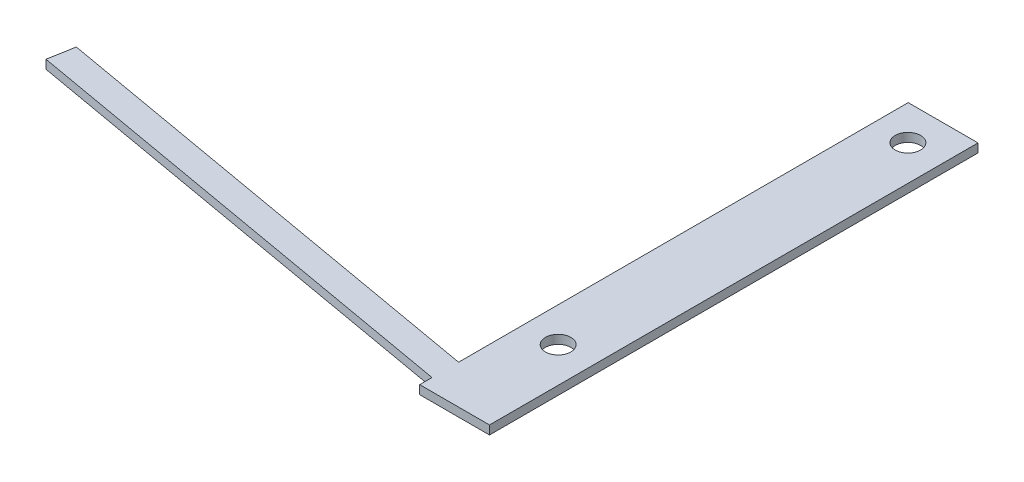
SolidWorks part; units mm, degrees
ref_plane "Front Plane" through (0, 0, 0) normal (0, 0, 1) x (1, 0, 0)
ref_plane "Top Plane" through (0, 0, 0) normal (0, 1, 0) x (1, 0, 0)
ref_plane "Right Plane" through (0, 0, 0) normal (1, 0, 0) x (0, 0, -1)
sketch "Sketch1" plane through (0, 0, 0) normal (0, 1, 0) x (1, 0, 0)
  line L1 (0, 101.5375) -> (12.7, 101.5375)
  line L2 (0, 101.5375) -> (0, 12.6375)
  line L3 (0, 12.6375) -> (12.7, 12.6375)
  line L4 (12.7, 101.5375) -> (12.7, 12.6375)
  circle A0 centre (6.2932, 95.1875) radius 2.31
  circle A5 centre (6.2932, 31.5375) radius 2.31
  point P4 (0, 0)
  dimension "D1" = 12.7
  dimension "D2" = 88.9
extrude "Boss-Extrude1" add sketch "Sketch1" along normal blind 1.5875
sketch "Sketch2" plane through (0, 0, 0) normal (0, -1, 0) x (1, 0, 0)
  line L0 (12.7, -12.6375) -> (-85.2884, -29.9155)
  line L1 (-85.2884, -29.9155) -> (-84.4614, -34.6057)
  line L2 (-84.4614, -34.6057) -> (12.7, -17.4735)
  line L3 (12.7, -17.4735) -> (12.7, -12.6375)
  line L4 (0, -12.6375) -> (0, -101.5375)
  line L5 (0, -101.5375) -> (12.7, -101.5375)
  line L6 (12.7, -101.5375) -> (12.7, -12.6375)
  line L7 (12.7, -12.6375) -> (0, -12.6375)
  line L8 (0, -12.6375) -> (0, -101.5375)
  line L9 (0, -101.5375) -> (12.7, -101.5375)
  line L10 (12.7, -101.5375) -> (12.7, -12.6375)
  line L11 (12.7, -12.6375) -> (0, -12.6375)
  line M6 (0, -12.6375) -> (0, -101.5375)
  dimension "D2" = 99.5
  dimension "D3" = 4.7625
  dimension "D4" = 80
  dimension "D1" = 0
extrude "Boss-Extrude2" add sketch "Sketch2" against normal up to surface (1.5875 mm away) contours L1 L2 L0 M6 region at (-42.4378, 0, -24.7739) up to face at (6.2932, 1.5875, -92.8775)
